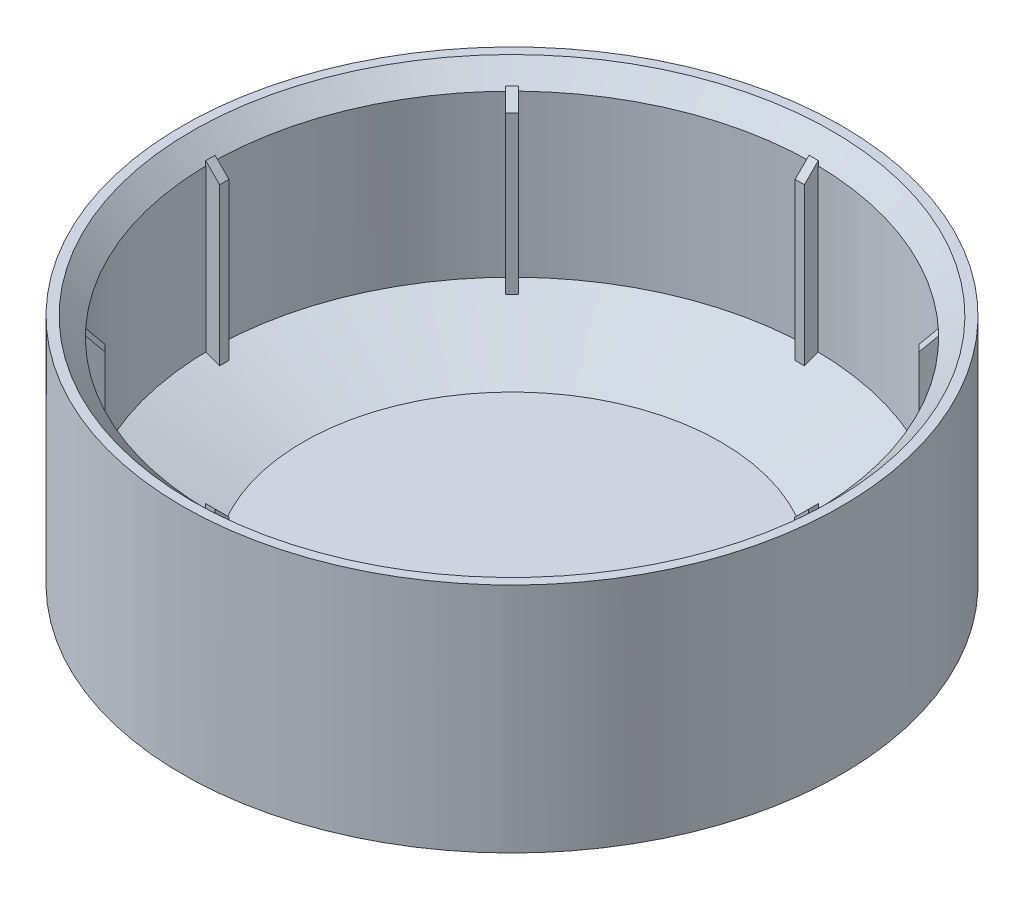
SolidWorks part; units mm, degrees
ref_plane "Front Plane" through (0, 0, 0) normal (0, 0, 1) x (1, 0, 0)
ref_plane "Top Plane" through (0, 0, 0) normal (0, 1, 0) x (1, 0, 0)
ref_plane "Right Plane" through (0, 0, 0) normal (1, 0, 0) x (0, 0, -1)
sketch "Sketch1" plane through (0, 0, 0) normal (0, 1, 0) x (1, 0, 0)
  circle A0 centre (0, 0) radius 32.5
  circle A1 centre (0, 0) radius 35.5
  dimension "D1" = 65
  dimension "D2" = 3
extrude "Boss-Extrude1" add sketch "Sketch1" along normal blind 20
sketch "Sketch2" plane through (0, 20, 0) normal (0, 1, 0) x (1, 0, 0)
  line L0 (-32.5, 0) -> (32.5, 0) construction
  line L1 (0, 32.5) -> (0, -32.5) construction
  line L2 (-22.981, 22.981) -> (22.981, -22.981) construction
  line L3 (22.981, 22.981) -> (-22.981, -22.981) construction
  line L4 (22.6247, 23.3318) -> (0.5, 1.2071)
  line L5 (-22.6247, -23.3318) -> (-0.5, -1.2071)
  line L6 (23.3318, 22.6247) -> (22.6247, 23.3318)
  line L7 (-22.6247, -23.3318) -> (-23.3318, -22.6247)
  line L8 (-32.4962, -0.5) -> (-1.2071, -0.5)
  line L9 (32.4955, -0.5417) -> (32.4962, 0.5)
  line L10 (32.4962, 0.5) -> (1.2071, 0.5)
  line L11 (-32.4962, 0.5) -> (-32.4962, -0.5)
  line L12 (-23.3318, 22.6247) -> (-1.2071, 0.5)
  line L13 (22.6247, -23.3318) -> (23.3318, -22.6247)
  line L14 (23.3318, -22.6247) -> (1.2071, -0.5)
  line L15 (-22.6247, 23.3318) -> (-23.3318, 22.6247)
  line L16 (0.5, 32.4962) -> (0.5, 1.2071)
  line L17 (0.5, -32.4962) -> (-0.5, -32.4962)
  line L18 (-0.5, -32.4962) -> (-0.5, -1.2071)
  line L19 (-0.5, 32.4962) -> (0.5, 32.4962)
  line L21 (0.5, -1.2071) -> (22.6247, -23.3318)
  line L23 (-0.5, 1.2071) -> (-0.5, 32.4962)
  line L24 (-1.2071, -0.5) -> (-23.3318, -22.6247)
  line L25 (-1.2071, 0.5) -> (-32.4962, 0.5)
  line L26 (-0.5, 1.2071) -> (-22.6247, 23.3318)
  line L27 (0.5, -1.2071) -> (0.5, -32.4962)
  line L28 (1.2071, 0.5) -> (23.3318, 22.6247)
  line L29 (1.2071, -0.5) -> (32.4955, -0.5417)
  circle A0 centre (0, 0) radius 32.5 construction
  dimension "D1" = 45
  dimension "D2" = 0
  dimension "D3" = 45
  dimension "D4" = 0
  dimension "D5" = 0.5
  dimension "D6" = 0.5
  dimension "D7" = 0.5
  dimension "D8" = 0.5
  dimension "D9" = 0.5
extrude "Boss-Extrude2" add sketch "Sketch2" against normal blind 20 separate body
sketch "Sketch3" plane through (0, 20, 0) normal (0, 1, 0) x (1, 0, 0)
  circle A0 centre (0, 0) radius 31
  dimension "D1" = 62
extrude "Cut-Extrude1" cut sketch "Sketch3" against normal blind 20
chamfer "Chamfer1" distance 2 angle 45 1 edges at (0, 20, 32.5)
chamfer "Chamfer2" distance 3 angle 45 1 edges at (0, 20, -31)
chamfer "Chamfer3" distance 3 angle 45 1 edges at (21.9203, 20, -21.9203)
chamfer "Chamfer4" distance 3 angle 45 1 edges at (31, 20, 0.0198)
chamfer "Chamfer5" distance 3 angle 45 1 edges at (21.9203, 20, 21.9203)
chamfer "Chamfer6" distance 3 angle 45 1 edges at (0, 20, 31)
chamfer "Chamfer7" distance 3 angle 45 1 edges at (-21.9203, 20, 21.9203)
chamfer "Chamfer8" distance 3 angle 45 1 edges at (-31, 20, 0)
chamfer "Chamfer9" distance 3 angle 45 1 edges at (-21.9203, 20, -21.9203)
sketch "Sketch4" plane through (0, 0, 0) normal (0, -1, 0) x (1, 0, 0)
  circle A0 centre (0, 0) radius 35.5
  circle A1 centre (0, 0) radius 32.5
extrude "Boss-Extrude5" add sketch "Sketch4" along normal blind 3
sketch "Sketch5" plane through (0, -3, 0) normal (0, -1, 0) x (1, 0, 0)
  circle A0 centre (0, 0) radius 35.5
extrude "Boss-Extrude6" add sketch "Sketch5" along normal blind 2
chamfer "Chamfer10" distance 10 angle 20 1 edges at (0, -3, -32.5) first distance on face at (0, -3, -32.5)
